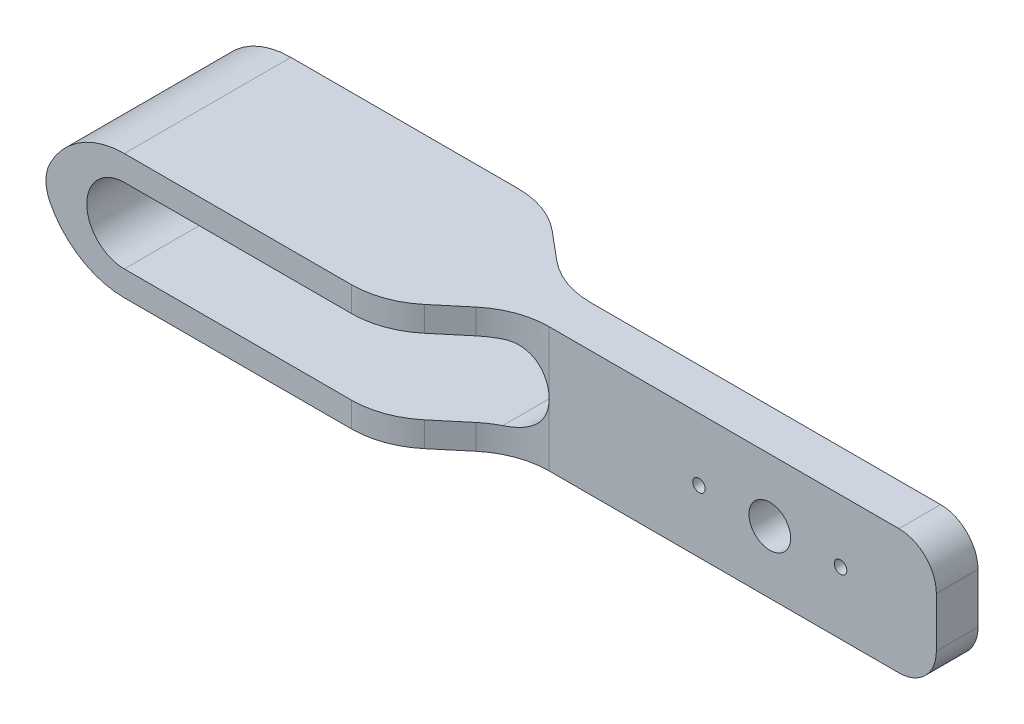
SolidWorks part; units mm, degrees
ref_plane "Plano frontal" through (0, 0, 0) normal (0, 0, 1) x (1, 0, 0)
ref_plane "Plano superior" through (0, 0, 0) normal (0, 1, 0) x (1, 0, 0)
ref_plane "Plano direito" through (0, 0, 0) normal (1, 0, 0) x (0, 0, -1)
sketch "Esboço1" plane through (0, 0, 0) normal (0, 0, 1) x (1, 0, 0)
  line L13 (-17.5, -6) -> (22.5, -6)
  line L14 (-17.5, -6) -> (-17.5, 9)
  line L15 (-17.5, 9) -> (22.5, 9)
  line L16 (22.5, -6) -> (22.5, 9)
  dimension "D3" = 15
  dimension "D4" = 40
extrude "Ressalto-extrusão1" add sketch "Esboço1" against normal blind 3 contours L13 L16 L15 L14 region at (2.5, 1.5, 0)
sketch "Esboço2" plane through (0, 0, 0) normal (0, 0, 1) x (1, 0, 0)
  line L0 (-17.5, 9) -> (22.5, -6) construction
  line L7 (-17.5, -6) -> (22.5, 9) construction
  circle A0 centre (2.5, 1.5) radius 2.5
  circle A4 centre (-6, 1.5) radius 0.75
  dimension "D1" = 1.5
  dimension "D3" = 5
  dimension "D2" = 8.5
sketch "Esboço3" plane through (0, 0, 0) normal (0, 0, 1) x (1, 0, 0)
  line L1 (-17.5, -6) -> (22.5, -6)
  line L2 (-17.5, -6) -> (-17.5, 9)
  line L3 (-17.5, 9) -> (22.5, 9)
  line L4 (22.5, -6) -> (22.5, 9)
extrude "Ressalto-extrusão2" add sketch "Esboço3" along normal blind 2
extrude "Corte-extrusão1" cut sketch "Esboço2" along normal up to surface and the other way up to surface up to face at (2.5, 1.5, 2) other way up to face at (2.5, 1.5, -3)
sketch "Esboço4" plane through (0, 9, 0) normal (0, 1, 0) x (1, 0, 0)
  line L0 (22.5, -2) -> (-17.5, -2) construction
  line L1 (6.2, -34.5) -> (-6.2, -34.5)
  line L2 (6.2, -34.5) -> (6.2, -11.5)
  line L3 (6.2, -11.5) -> (-6.2, -11.5)
  line L4 (-6.2, -34.5) -> (-6.2, -11.5)
  line L5 (-17.5, 3) -> (22.5, 3) construction
  line L6 (17.5, -2) -> (-12.5, -2)
  line L7 (17.5, -2) -> (17.5, -42)
  line L8 (17.5, -42) -> (-12.5, -42)
  line L9 (-12.5, -2) -> (-12.5, -42)
  line L10 (-12.5, -2) -> (17.5, -2)
  line L11 (-12.5, -2) -> (-12.5, 3)
  line L12 (-12.5, 3) -> (17.5, 3)
  line L13 (17.5, -2) -> (17.5, 3)
  circle A0 centre (0, -9.75) radius 1.25
  circle A1 centre (0, -36.25) radius 1.25
  point P6 (0, -34.5)
  point P13 (2.5, -2)
  point P14 (2.5, -42)
  line M5 (-17.5, -2) -> (22.5, -2)
  line M7 (22.5, 3) -> (-17.5, 3)
  dimension "D6" = 7.75
  dimension "D7" = 2.5
  dimension "D8" = 26.5
  dimension "D1" = 9.5
  dimension "D2" = 23
  dimension "D3" = 12.4
  dimension "D4" = 30
  dimension "D5" = 40
extrude "Ressalto-extrusão3" [suppressed] add sketch "Esboço4" against normal blind 3 contours L13 L11 M5 M7 | L9 L8 L7 L1 L4 L3 L2 M5
fillet "Filete2" [suppressed] radius 5
fillet "Filete3" [suppressed] radius 10
sketch "Esboço5" plane through (-17.5, 0, 0) normal (-1, 0, 0) x (0, 0, 1)
  line L0 (-3, 9) -> (2, 9) construction
  line L1 (-10.5, -6) -> (9.5, -6)
  line L2 (-10.5, -6) -> (-10.5, 9)
  line L3 (-10.5, 9) -> (9.5, 9)
  line L4 (9.5, -6) -> (9.5, 9)
  line L5 (-3, -6) -> (2, -6) construction
  point P13 (-0.5, -6)
  point P14 (-0.5, -6)
  dimension "D1" = 20
extrude "Ressalto-extrusão4" add sketch "Esboço5" along normal blind 60
chamfer "Chanfro1" distance 16 angle 50 2 edges at (-17.5, 1.5, 9.5) (-17.5, 1.5, -10.5) first distance on face at (-17.5, 1.5, 5.75) first distance on face at (-17.5, 1.5, -6.75)
fillet "Filete4" radius 10 6 edges at (-36.5681, 1.5, 9.5) (-27.6299, 1.5, 2) (-77.5, 9, -0.5) (-77.5, -6, -0.5) (-36.5681, 1.5, -10.5) (-27.6299, 1.5, -3)
sketch "Esboço6" plane through (0, 0, 9.5) normal (0, 0, 1) x (1, 0, 0)
  line L0 (-43.2078, 6) -> (-67.5, 6)
  line L1 (-67.5, -3) -> (-43.2078, -3)
  line L2 (-43.2078, -3) -> (-43.2078, 6) construction
  line L3 (-40.2078, 9) -> (-67.5, 9)
  line L4 (-67.5, -6) -> (-40.2078, -6)
  line L5 (-40.2078, -6) -> (-40.2078, 9)
  line L6 (-40.2078, 9) -> (-67.5, 9) construction
  line L7 (-67.5, -6) -> (-40.2078, -6) construction
  line L8 (-40.2078, -6) -> (-40.2078, 9) construction
  line L9 (-43.2078, 6) -> (-23.9902, 6)
  line L10 (-23.9902, 9) -> (-23.9902, -6) construction
  line L11 (-43.2078, -3) -> (-23.9902, -3)
  line L12 (-23.9902, -3) -> (-23.9902, 6)
  arc A0 (-67.5, 6) -> (-74.0383, 1.5) centre (-67.5, -1) ccw
  arc A1 (-74.0383, 1.5) -> (-67.5, -3) centre (-67.5, 4) ccw
  arc A2 (-67.5, 9) -> (-77.1825, 1.5) centre (-67.5, -1) ccw
  arc A3 (-77.1825, 1.5) -> (-67.5, -6) centre (-67.5, 4) ccw
  arc A4 (-67.5, 9) -> (-77.1825, 1.5) centre (-67.5, -1) ccw construction
  arc A5 (-77.1825, 1.5) -> (-67.5, -6) centre (-67.5, 4) ccw construction
  dimension "D1" = 0
  dimension "D2" = 3
extrude "Corte-extrusão2" cut sketch "Esboço6" against normal through all
fillet "Filete5" radius 4.5 4 edges at (-23.9902, -3, -0.5) (-23.9902, 6, -0.5) (22.5, -6, -0.5) (22.5, 9, -0.5)
pattern_circular "CirPattern1" count 2 over 360 about axis through (2.5, 1.5, 2) along (0, 0, -1) of "Corte-extrusão1"
fillet "Fillet1" radius 4.5 2 edges at (-77.1825, 1.5, -0.5) (-74.0383, 1.5, -0.5)
move or copy body "Body-Move/Copy1" [suppressed] bodies to move or copy 109
